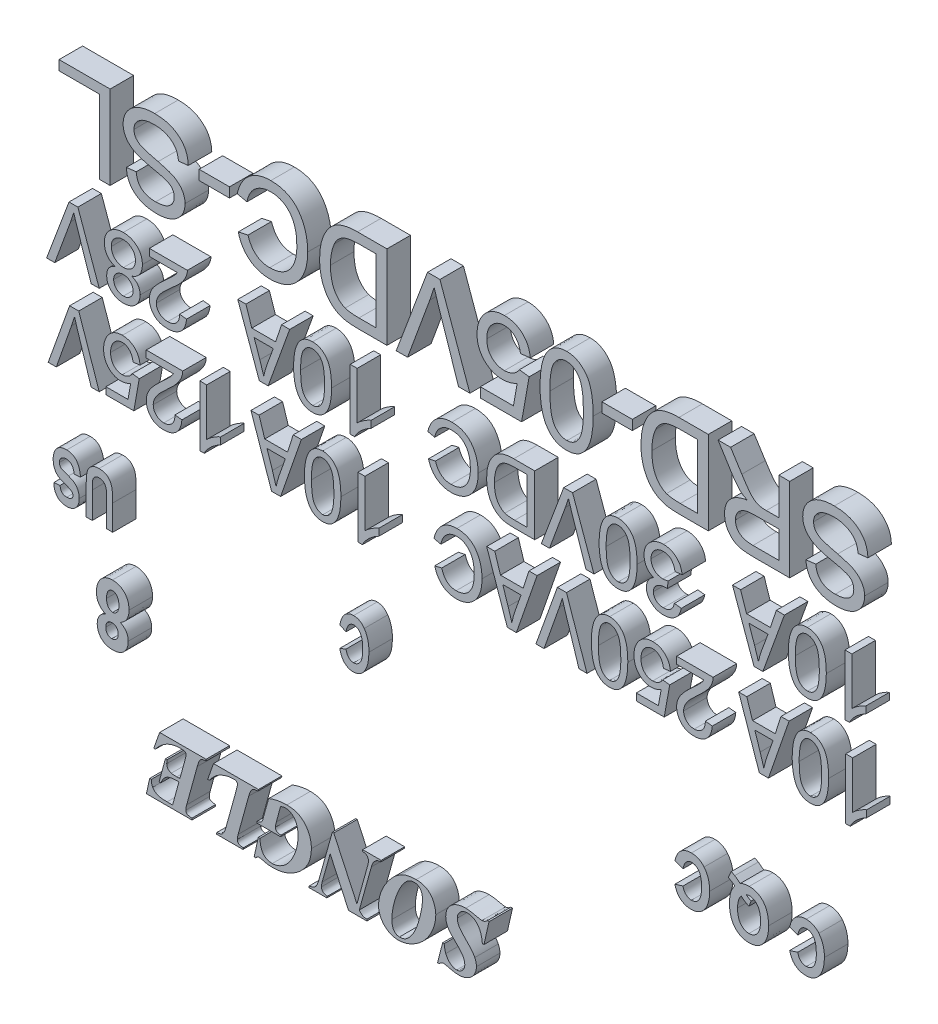
SolidWorks part; units mm, degrees
ref_plane "前基準面" through (0, 0, 0) normal (0, 0, 1) x (1, 0, 0)
ref_plane "上基準面" through (0, 0, 0) normal (0, 1, 0) x (1, 0, 0)
ref_plane "右基準面" through (0, 0, 0) normal (1, 0, 0) x (0, 0, -1)
sketch "草圖1" plane through (0, 0, 0) normal (0, 0, 1) x (1, 0, 0)
  line L0 (-29.5257, 13.9306) -> (-45.8055, 13.9306) construction
  line L1 (-29.5257, 11.413) -> (-46.0357, 11.413) construction
  line L2 (-29.5257, 9.508) -> (-46.7501, 9.508) construction
  line L3 (-40.237, 6.809) -> (-48.167, 6.809) construction
  line L4 (-45.3137, 4.8965) -> (-46.1074, 4.8965) construction
  line L5 (-37.7614, 2.6056) -> (-44.9448, 2.6056) construction
  line L6 (-30.536, 6.0286) -> (-33.5367, 6.0286) construction
  text T0 "SRD-05VDC-SL-C" font "ARIAL NARROW" height 1.778
  text T1 "10A  30VDC  10A  28VDC" font "ARIAL NARROW" height 1.27
  text T2 "10A 250VAC  10A 125VAC" font "ARIAL NARROW" height 1.27
  text T3 "<b>C                 US</b>" font "ARIAL NARROW" height 1.016
  text T4 "<b>8</b>" font "ARIAL NARROW" height 1.27
  text T5 "<b><i>SONGLE</i></b>" font "TIMES NEW ROMAN" height 1.27
  text T6 "<b>C Q C</b>" font "ARIAL NARROW" height 1.016
extrude "填料-伸長1" add sketch "草圖1" along normal blind 0.5
